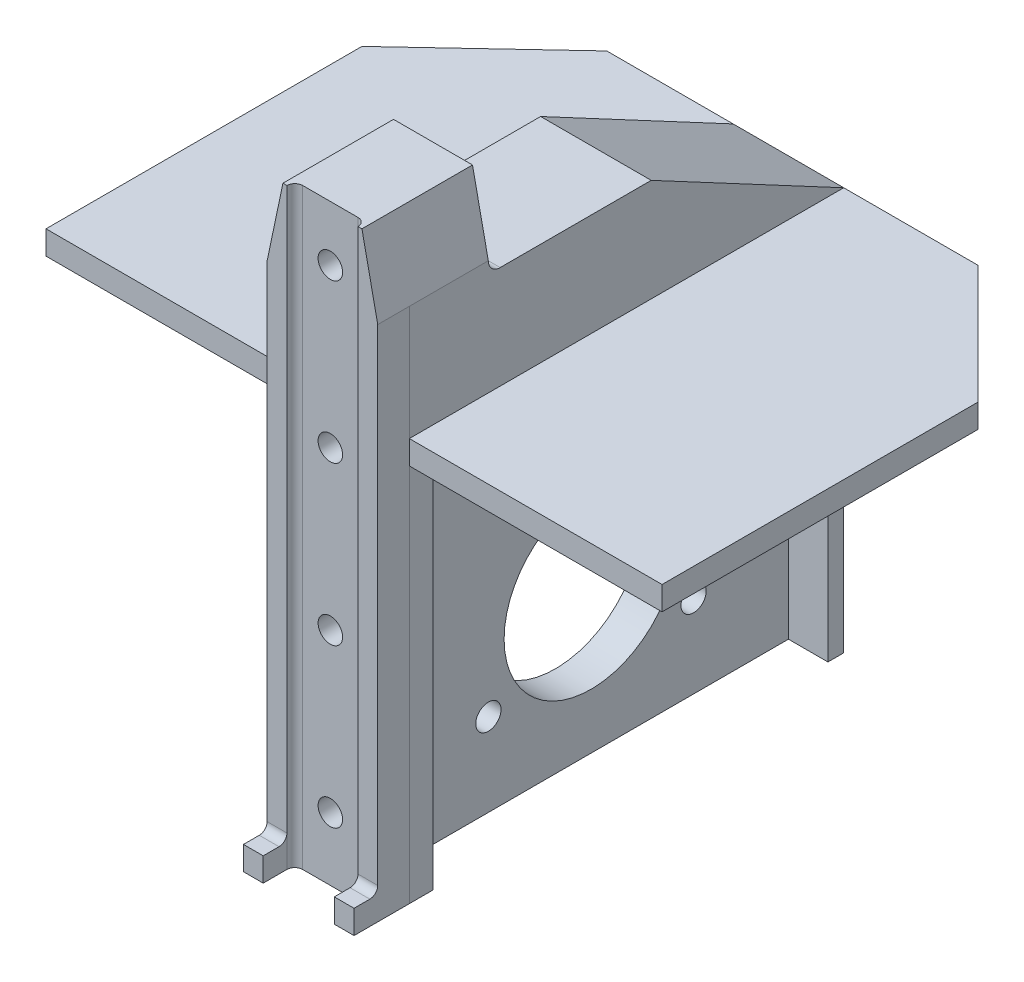
SolidWorks part; units mm, degrees
ref_plane "前视基准面" through (0, 0, 0) normal (0, 0, 1) x (1, 0, 0)
ref_plane "上视基准面" through (0, 0, 0) normal (0, 1, 0) x (1, 0, 0)
ref_plane "右视基准面" through (0, 0, 0) normal (1, 0, 0) x (0, 0, -1)
sketch "草图4" plane through (0, 0, 0) normal (0, 0, 1) x (1, 0, 0)
  line L0 (-14.6792, 23.9245) -> (63.3208, 23.9245)
  line L1 (63.3208, 23.9245) -> (63.3208, 20.9245)
  line L2 (63.3208, 20.9245) -> (31.3208, 20.9245)
  line L3 (31.3208, 20.9245) -> (31.3208, -37.0755)
  line L4 (31.3208, -37.0755) -> (17.3208, -37.0755)
  line L5 (17.3208, -37.0755) -> (17.3208, 20.9245)
  line L6 (17.3208, 20.9245) -> (-14.6792, 20.9245)
  line L7 (-14.6792, 20.9245) -> (-14.6792, 23.9245)
  dimension "D1" = 32
  dimension "D2" = 32
  dimension "D3" = 58
  dimension "D4" = 58
  dimension "D5" = 3
  dimension "D6" = 14
extrude "凸台-拉伸2" add sketch "草图4" along normal blind 55
sketch "草图5" plane through (17.3208, 0, 0) normal (-1, 0, 0) x (0, 0, 1)
  line L0 (55, 20.9245) -> (0, 20.9245) construction
  line L1 (2, 20.9245) -> (52, 20.9245)
  line L2 (2, 20.9245) -> (2, -37.0755)
  line L3 (2, -37.0755) -> (52, -37.0755)
  line L4 (52, 20.9245) -> (52, -37.0755)
  line L5 (55, -37.0755) -> (0, -37.0755) construction
  line L6 (0, 20.9245) -> (0, -37.0755) construction
  line L7 (55, 20.9245) -> (55, -37.0755) construction
  dimension "D1" = 2
  dimension "D2" = 3
extrude "切除-拉伸2" cut sketch "草图5" against normal blind 4.5
sketch "草图6" plane through (21.8208, 0, 0) normal (-1, 0, 0) x (0, 0, 1)
  line L0 (27, 20.9245) -> (27, -37.0755) construction
  line L1 (52, 20.9245) -> (2, 20.9245) construction
  line L2 (2, -37.0755) -> (52, -37.0755) construction
  line L3 (55, 20.9245) -> (0, 20.9245) construction
  circle A0 centre (27, -9.0755) radius 11
  circle A1 centre (27, 5.9245) radius 1.6
  circle A5 centre (39.9904, -16.5755) radius 1.6
  circle A6 centre (14.0096, -16.5755) radius 1.6
  point P10 (27, -9.0755)
  point P16 (20.5, -15.7493)
  point P17 (20.5, -22.0755)
  point P18 (22.5, -8.2302)
  point P19 (24.5, -7.0755)
  point P22 (25.75, -2.7972)
  point P23 (27, -2.0755)
  point P24 (26.4226, -8.0755)
  point P26 (27, -9.0755)
  dimension "D1" = 3.2
  dimension "D2" = 22
  dimension "D3" = 15
  dimension "D5" = 30
  dimension "D4" = 3
extrude "切除-拉伸3" cut sketch "草图6" against normal blind 4.5
sketch "草图8" plane through (0, 0, 55) normal (0, 0, 1) x (1, 0, 0)
  line L0 (17.3208, 23.9245) -> (17.3208, 47.9245)
  line L1 (63.3208, 23.9245) -> (-14.6792, 23.9245) construction
  line L2 (17.3208, 47.9245) -> (31.3208, 47.9245)
  line L3 (31.3208, 47.9245) -> (31.3208, 23.9245)
  line L4 (31.3208, 23.9245) -> (17.3208, 23.9245)
  dimension "D1" = 24
extrude "凸台-拉伸3" add sketch "草图8" against normal blind 55
sketch "草图9" plane through (0, 0, 55) normal (0, 0, 1) x (1, 0, 0)
  line L0 (24.3208, 47.9245) -> (24.3208, -37.0755) construction
  line L1 (31.3208, 47.9245) -> (17.3208, 47.9245) construction
  line L2 (17.3208, -37.0755) -> (31.3208, -37.0755) construction
  circle A0 centre (24.3208, 40.9245) radius 1.55
  circle A1 centre (24.3208, 20.9245) radius 1.55
  circle A2 centre (24.3208, 0.9245) radius 1.55
  circle A3 centre (24.3208, -19.0755) radius 1.55
  dimension "D1" = 3.1
  dimension "D4" = 20
  dimension "D2" = 7
  dimension "D3" = 4
extrude "切除-拉伸4" cut sketch "草图9" against normal blind 4
sketch "草图13" plane through (0, 0, 55) normal (0, 0, 1) x (1, 0, 0)
  line L0 (17.3208, 47.9245) -> (19.3208, 47.9245)
  line L1 (31.3208, 47.9245) -> (17.3208, 47.9245) construction
  line L2 (19.3208, 47.9245) -> (17.3208, 38.4245)
  line L3 (17.3208, 47.9245) -> (17.3208, 23.9245) construction
  line L4 (17.3208, 38.4245) -> (17.3208, 47.9245)
  line L5 (29.3208, 47.9245) -> (31.3208, 47.9245)
  line L6 (31.3208, 47.9245) -> (31.3208, 38.4245)
  line L7 (31.3208, 23.9245) -> (31.3208, 47.9245) construction
  line L8 (31.3208, 38.4245) -> (29.3208, 47.9245)
  dimension "D1" = 2
  dimension "D2" = 2
  dimension "D3" = 9.5
  dimension "D4" = 9.5
extrude "切除-拉伸8" cut sketch "草图13" against normal blind 55
sketch "草图20" plane through (31.3208, 0, 0) normal (1, 0, 0) x (0, 0, -1)
  line L0 (0, 23.9245) -> (0, 47.9245)
  line L1 (0, 47.9245) -> (-55, 47.9245) construction
  line L2 (0, 47.9245) -> (-45, 47.9245)
  line L3 (-45, 47.9245) -> (0, 23.9245)
  dimension "D1" = 10
extrude "切除-拉伸12" cut sketch "草图20" against normal blind 15
sketch "草图21" plane through (0, 23.9245, 0) normal (0, 1, 0) x (1, 0, 0)
  line L0 (-14.6792, 0) -> (1.3208, 0)
  line L2 (17.3208, 0) -> (-14.6792, 0) construction
  line L3 (1.3208, 0) -> (-14.6792, -15)
  line L4 (-14.6792, -55) -> (-14.6792, 0) construction
  line L5 (-14.6792, -15) -> (-14.6792, 0)
  line L6 (48.3208, 0) -> (63.3208, 0)
  line L7 (63.3208, 0) -> (31.3208, 0) construction
  line L8 (63.3208, 0) -> (63.3208, -15)
  line L9 (63.3208, -55) -> (63.3208, 0) construction
  line L10 (63.3208, -15) -> (48.3208, 0)
  dimension "D1" = 15
  dimension "D2" = 15
  dimension "D3" = 15
extrude "切除-拉伸13" cut sketch "草图21" against normal blind 3
sketch "草图23" plane through (31.3208, 0, 0) normal (1, 0, 0) x (0, 0, -1)
  line L0 (-52, -37.0755) -> (-52, 20.9245)
  line L1 (-55, -37.0755) -> (0, -37.0755) construction
  line L2 (-52, 20.9245) -> (-2, 20.9245)
  line L3 (-2, 20.9245) -> (-2, -37.0755)
  line L4 (-2, -37.0755) -> (-52, -37.0755)
  line L5 (-55, -37.0755) -> (-55, 20.9245) construction
  line L6 (0, -37.0755) -> (0, 20.9245) construction
  line L7 (-55, 20.9245) -> (-15, 20.9245) construction
  dimension "D1" = 3
  dimension "D2" = 2
extrude "切除-拉伸14" cut sketch "草图23" against normal blind 5
sketch "草图24" plane through (0, 0, 55) normal (0, 0, 1) x (1, 0, 0)
  line L0 (17.3208, -37.0755) -> (17.3208, -27.0755)
  line L1 (17.3208, 20.9245) -> (17.3208, -37.0755) construction
  line L2 (17.3208, -27.0755) -> (31.3208, -27.0755)
  line L3 (31.3208, -37.0755) -> (31.3208, 20.9245) construction
  line L4 (31.3208, -27.0755) -> (31.3208, -37.0755)
  line L5 (31.3208, -37.0755) -> (17.3208, -37.0755)
  dimension "D1" = 10
extrude "切除-拉伸15" cut sketch "草图24" against normal blind 56
fillet "圆角1" radius 2 1 edges at (21.8208, 20.9245, 27)
fillet "圆角2" radius 2 1 edges at (26.3208, 20.9245, 27)
fillet "圆角3" radius 0.5 6 edges at (18.5708, 20.9245, 52) (21.235, 20.3387, 52) (29.8208, 20.9245, 52) (26.9065, 20.3387, 52) (21.8208, -4.0755, 52) (26.3208, -4.0755, 52)
sketch "草图25" plane through (0, 47.9245, 0) normal (0, 1, 0) x (1, 0, 0)
  line L0 (19.3208, -45) -> (17.3208, -45)
  line L1 (17.3208, 0) -> (17.3208, -55) construction
  line L2 (17.3208, -45) -> (17.3208, -24)
  line L3 (17.3208, 0) -> (17.3208, -27.1875) construction
  line L4 (17.3208, -24) -> (31.3208, -24)
  line L5 (31.3208, -27.1875) -> (31.3208, 0) construction
  line L6 (31.3208, -24) -> (31.3208, -45)
  line L7 (31.3208, 0) -> (31.3208, -55) construction
  line L8 (31.3208, -45) -> (19.3208, -45)
  dimension "D1" = 21
extrude "切除-拉伸16" cut sketch "草图25" against normal blind 11
fillet "圆角4" radius 1.5 1 edges at (24.3208, 36.9245, 45)
sketch "草图26" plane through (0, 0, 55) normal (0, 0, 1) x (1, 0, 0)
  line L0 (17.3208, -27.0755) -> (31.3208, -27.0755)
  line L1 (31.3208, -27.0755) -> (31.3208, 38.4245)
  line L2 (31.3208, 38.4245) -> (29.3208, 47.9245)
  line L3 (29.3208, 47.9245) -> (19.3208, 47.9245)
  line L4 (19.3208, 47.9245) -> (17.3208, 38.4245)
  line L5 (17.3208, 38.4245) -> (17.3208, -27.0755)
  circle A0 centre (24.3208, -19.0755) radius 1.55 construction
  circle A1 centre (24.3208, 0.9245) radius 1.55 construction
  circle A2 centre (24.3208, 20.9245) radius 1.55 construction
  circle A3 centre (24.3208, 40.9245) radius 1.55 construction
  circle A4 centre (24.3208, -19.0755) radius 1.55
  circle A5 centre (24.3208, 0.9245) radius 1.55
  circle A6 centre (24.3208, 20.9245) radius 1.55
  circle A7 centre (24.3208, 40.9245) radius 1.55
extrude "凸台-拉伸4" add sketch "草图26" along normal blind 4
sketch "草图27" plane through (0, 0, 59) normal (0, 0, 1) x (1, 0, 0)
  line L0 (24.3208, -27.0755) -> (24.3208, 47.9245) construction
  line L1 (17.3208, -27.0755) -> (31.3208, -27.0755) construction
  line L2 (29.3208, 47.9245) -> (19.3208, 47.9245) construction
  line L4 (19.8208, 47.9245) -> (28.8208, 47.9245)
  line L5 (19.8208, 47.9245) -> (19.8208, -27.0755)
  line L6 (19.8208, -27.0755) -> (28.8208, -27.0755)
  line L7 (28.8208, 47.9245) -> (28.8208, -27.0755)
  dimension "D1" = 9
  dimension "D2" = 4.5
extrude "切除-拉伸17" cut sketch "草图27" against normal blind 1
fillet "圆角5" radius 1 2 edges at (28.8208, 10.4245, 58) (19.8208, 10.4245, 58)
sketch "草图28" plane through (0, 0, 59) normal (0, 0, 1) x (1, 0, 0)
  line L0 (19.8208, 47.9245) -> (19.8208, -27.0755) construction
  line L1 (17.3208, -27.0755) -> (19.8208, -27.0755)
  line L2 (17.3208, -27.0755) -> (17.3208, -24.0755)
  line L3 (17.3208, -24.0755) -> (19.8208, -24.0755)
  line L4 (19.8208, -27.0755) -> (19.8208, -24.0755)
  line L5 (31.3208, -27.0755) -> (31.3208, 38.4245) construction
  line L6 (28.8208, -27.0755) -> (31.3208, -27.0755)
  line L7 (28.8208, -27.0755) -> (28.8208, -24.0755)
  line L8 (28.8208, -24.0755) -> (31.3208, -24.0755)
  line L9 (31.3208, -27.0755) -> (31.3208, -24.0755)
  dimension "D1" = 3
  dimension "D2" = 3
extrude "凸台-拉伸5" add sketch "草图28" along normal blind 3
fillet "圆角6" radius 1 2 edges at (18.5708, -24.0755, 59) (30.0708, -24.0755, 59)
sketch "草图29" plane through (0, 0, 51) normal (0, 0, 1) x (1, 0, 0)
  circle A0 centre (24.3208, 40.9245) radius 1.55
extrude "切除-拉伸18" cut sketch "草图29" against normal blind 11
